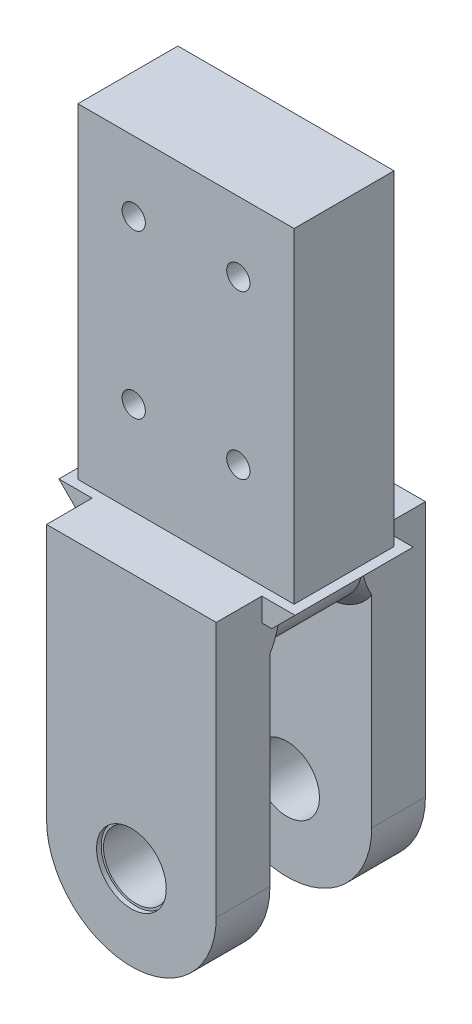
SolidWorks part; units mm, degrees
ref_plane "Front Plane" through (0, 0, 0) normal (0, 0, 1) x (1, 0, 0)
ref_plane "Top Plane" through (0, 0, 0) normal (0, 1, 0) x (1, 0, 0)
ref_plane "Right Plane" through (0, 0, 0) normal (1, 0, 0) x (0, 0, -1)
sketch "Sketch1" plane through (0, 0, 0) normal (0, 0, 1) x (1, 0, 0)
  line L0 (-23.25, 0) -> (-23.25, 125)
  line L1 (-23.25, 125) -> (23.25, 125)
  line L2 (23.25, 125) -> (23.25, 0)
  line L4 (-11.25, 110) -> (11.25, 110) construction
  line L5 (-11.25, 110) -> (-11.25, 75) construction
  line L6 (-11.25, 75) -> (11.25, 75) construction
  line L7 (11.25, 110) -> (11.25, 75) construction
  circle A0 centre (0, 0) radius 7
  arc A1 (-23.25, 0) -> (23.25, 0) centre (0, 0) ccw
  circle A2 centre (-11.25, 110) radius 2.5
  circle A3 centre (11.25, 110) radius 2.5
  circle A4 centre (11.25, 75) radius 2.5
  circle A5 centre (-11.25, 75) radius 2.5
  point P13 (0, 75)
  dimension "D1" = 14
  dimension "D4" = 5
  dimension "D2" = 46.5
  dimension "D3" = 125
  dimension "D5" = 35
  dimension "D6" = 15
  dimension "D7" = 22.5
extrude "Boss-Extrude1" add sketch "Sketch1" along normal mid plane 45
sketch "Sketch2" plane through (23.25, 0, 0) normal (1, 0, 0) x (0, 0, -1)
  line L0 (-22.5, -23.25) -> (22.5, -23.25) construction
  line L1 (-10.95, 40) -> (10.95, 40)
  line L2 (-10.95, 40) -> (-10.95, -23.25)
  line L3 (-10.95, -23.25) -> (10.95, -23.25)
  line L4 (10.95, 40) -> (10.95, -23.25)
  line L5 (-22.5, 0) -> (22.5, 0) construction
  point P8 (0, 0)
  point P9 (0, 40)
  dimension "D1" = 21.9
  dimension "D2" = 40
extrude "Cut-Extrude1" cut sketch "Sketch2" against normal through all
sketch "Sketch3" plane through (0, 0, 22.5) normal (0, 0, 1) x (1, 0, 0)
  circle A0 centre (0, 0) radius 7.5
  dimension "D1" = 15
extrude "Cut-Extrude2" cut sketch "Sketch3" against normal blind 1
sketch "Sketch4" plane through (0, 0, -22.5) normal (0, 0, -1) x (-1, 0, 0)
  circle A0 centre (0, 0) radius 7.5
  dimension "D1" = 15
extrude "Cut-Extrude3" cut sketch "Sketch4" against normal blind 1
sketch "Sketch5" plane through (23.25, 0, 0) normal (1, 0, 0) x (0, 0, -1)
  line L1 (-22.5, 125) -> (-12.7, 125)
  line L2 (-22.5, 125) -> (-22.5, 55)
  line L3 (-22.5, 55) -> (-12.7, 55)
  line L4 (-12.7, 125) -> (-12.7, 55)
  line L5 (22.5, 125) -> (12.7, 125)
  line L6 (22.5, 125) -> (22.5, 55)
  line L7 (22.5, 55) -> (12.7, 55)
  line L8 (12.7, 125) -> (12.7, 55)
  dimension "D1" = 70
  dimension "D2" = 25.4
extrude "Cut-Extrude4" cut sketch "Sketch5" against normal through all
sketch "Sketch6" plane through (0, 0, 22.5) normal (0, 0, 1) x (1, 0, 0)
  line L0 (-18.25, 0) -> (-18.25, 55)
  line L1 (-23.25, 55) -> (23.25, 55) construction
  line L3 (-23.25, 55) -> (23.25, 55) construction
  line L4 (18.25, 55) -> (18.25, 0)
  line L5 (-18.25, 55) -> (-23.25, 55)
  line L6 (-23.25, 55) -> (-23.25, -23.25)
  line L7 (-23.25, -23.25) -> (23.25, -23.25)
  line L8 (23.25, -23.25) -> (23.25, 55)
  line L9 (23.25, 55) -> (18.25, 55)
  arc A0 (-18.25, 0) -> (18.25, 0) centre (0, 0) ccw
  arc A1 (-23.25, 0) -> (23.25, 0) centre (0, 0) ccw construction
  point P19 (0, -23.25)
  dimension "D1" = 5
extrude "Cut-Extrude5" cut sketch "Sketch6" against normal through all
sketch "Sketch8" plane through (0, 125, 0) normal (0, 1, 0) x (1, 0, 0)
  line L5 (23.25, -12.7) -> (23.25, 12.7) construction
  line L10 (-23.25, 12.7) -> (23.25, 12.7)
  line L11 (-23.25, 12.7) -> (-23.25, 10.75)
  line L12 (-23.25, 10.75) -> (23.25, 10.75)
  line L13 (23.25, 12.7) -> (23.25, 10.75)
  line L15 (23.25, -10.75) -> (-23.25, -10.75)
  line L16 (23.25, -10.75) -> (23.25, -12.7)
  line L17 (23.25, -12.7) -> (-23.25, -12.7)
  line L18 (-23.25, -10.75) -> (-23.25, -12.7)
  dimension "D1" = 21.5
extrude "Cut-Extrude6" cut sketch "Sketch8" against normal up to surface (70 mm away) up to face at (0, 55, -17.6)
sketch "Sketch9" plane through (0, 55, 0) normal (0, 1, 0) x (1, 0, 0)
  line L1 (-25.4, 12.7) -> (25.4, 12.7)
  line L2 (-25.4, 12.7) -> (-25.4, -12.7)
  line L3 (-25.4, -12.7) -> (25.4, -12.7)
  line L4 (25.4, 12.7) -> (25.4, -12.7)
  point P9 (0, 12.7)
  point P13 (-25.4, 0)
  dimension "D1" = 25.4
  dimension "D2" = 50.8
extrude "Boss-Extrude2" add sketch "Sketch9" against normal blind 5
fillet "Fillet1" radius 10 2 edges at (18.25, 40, 0) (-18.25, 40, 0)
chamfer "Chamfer1" distance 5 angle 45 2 edges at (-25.4, 50, 0) (25.4, 50, 0)
chamfer "Chamfer2" distance 2 angle 45 6 edges at (-15.3211, 42.9289, -10.95) (15.3211, 42.9289, -10.95) (0, 40, -10.95) (-15.3211, 42.9289, 10.95) (15.3211, 42.9289, 10.95) (0, 40, 10.95)
